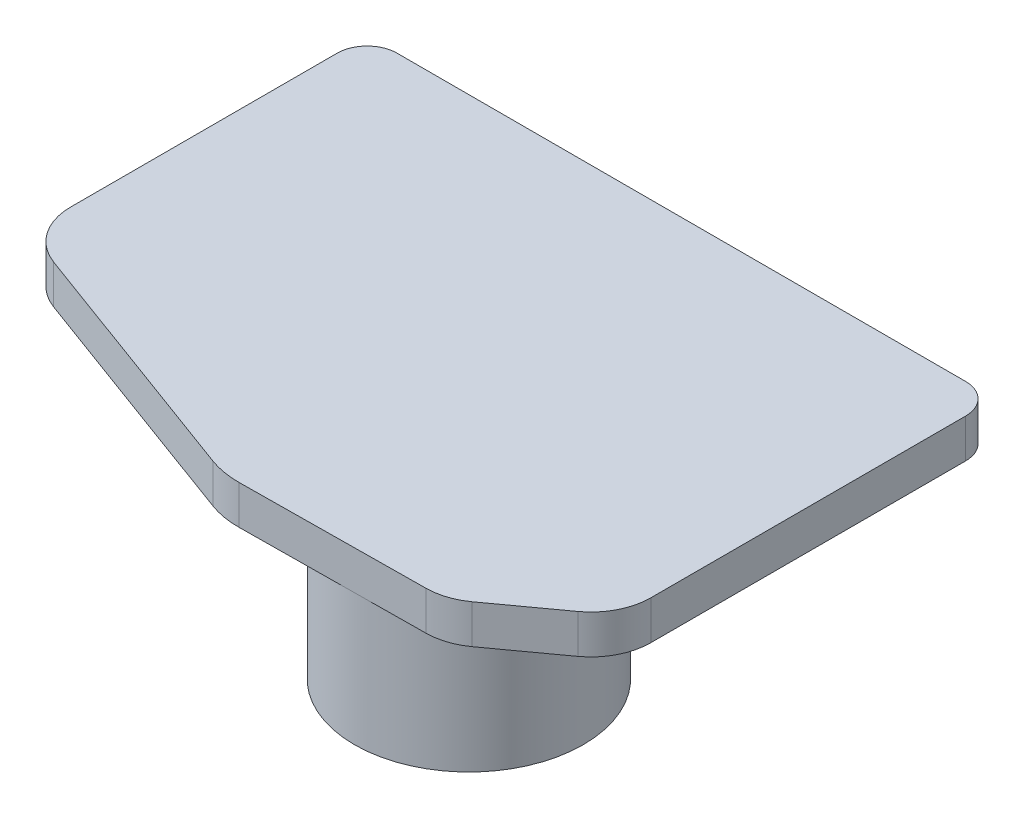
SolidWorks part; units mm, degrees
ref_plane "Front Plane" through (0, 0, 0) normal (0, 0, 1) x (1, 0, 0)
ref_plane "Top Plane" through (0, 0, 0) normal (0, 1, 0) x (1, 0, 0)
ref_plane "Right Plane" through (0, 0, 0) normal (1, 0, 0) x (0, 0, -1)
sketch "Sketch1" plane through (0, 0, 0) normal (0, 1, 0) x (1, 0, 0)
  line L0 (96.7455, -56.3537) -> (76.301, -71.1878)
  line L1 (-95, 75) -> (95, 75)
  line L2 (-105, 65) -> (-105, -24.047)
  line L3 (2.8917, -75.6134) -> (64.7542, -74.999)
  line L4 (105, 65) -> (105, -40.1659)
  line L5 (-105, 75) -> (87.8903, -62.7788) construction
  line L6 (-70.809, -50.5778) -> (105, 75) construction
  line L7 (-91.905, -42.8173) -> (-7.7637, -73.7702)
  arc A0 (96.7455, -56.3537) -> (105, -40.1659) centre (85, -40.1659) ccw
  arc A1 (64.7542, -74.999) -> (76.301, -71.1878) centre (64.5555, -55) ccw
  arc A2 (2.8917, -75.6134) -> (-7.7637, -73.7702) centre (2.5938, -45.6149) cw
  arc A3 (-91.905, -42.8173) -> (-105, -24.047) centre (-85, -24.047) cw
  arc A4 (-105, 65) -> (-95, 75) centre (-95, 65) cw
  arc A5 (105, 65) -> (95, 75) centre (95, 65) ccw
  point P0 (0, -38)
  dimension "D1" = 20
  dimension "D2" = 20
  dimension "D4" = 30
  dimension "D5" = 20
  dimension "D6" = 10
  dimension "D7" = 10
  dimension "D3" = 210
sketch "Sketch3" plane through (0, 0, 0) normal (0, 1, 0) x (1, 0, 0)
  line L2 (2.8917, -75.6134) -> (64.7542, -74.999) construction
  line L3 (105, 65) -> (105, -40.1659) construction
  circle A0 centre (41, -37) radius 38.233
  dimension "D1" = 64
extrude "Boss-Extrude2" add sketch "Sketch1" along normal blind 13
extrude "Boss-Extrude3" add sketch "Sketch3" against normal blind 44
ref_point "Point2"
ref_point "Point3"
ref_axis "Axis1" through (41, 0, 37) along (0, -1, 0)
